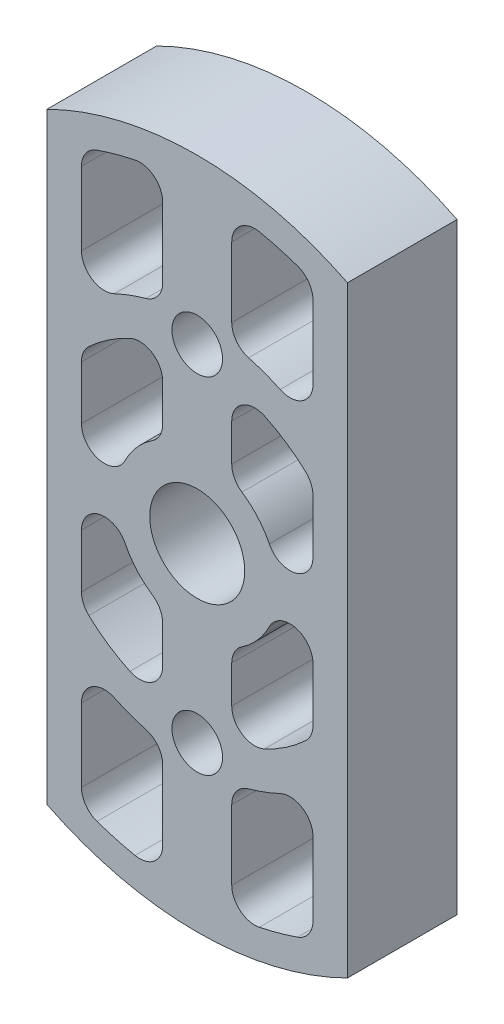
SolidWorks part; units mm, degrees
material "6061 Alloy"
ref_plane "Front Plane" through (0, 0, 0) normal (0, 0, 1) x (1, 0, 0)
ref_plane "Top Plane" through (0, 0, 0) normal (0, 1, 0) x (1, 0, 0)
ref_plane "Right Plane" through (0, 0, 0) normal (1, 0, 0) x (0, 0, -1)
sketch "Sketch1" plane through (0, 0, 0) normal (0, 0, 1) x (1, 0, 0)
  circle A0 centre (0, 0) radius 29.25
  dimension "D1" = 58.5
extrude "3/8" add sketch "Sketch1" along normal blind 9.525
sketch "Sketch2" plane through (0, 0, 9.525) normal (0, 0, 1) x (1, 0, 0)
  line L0 (0, 0) -> (0, 37.0794) construction
  line L1 (0, 0) -> (-34.7106, 0) construction
  line L2 (-3, 24.2193) -> (-3, 18.1547)
  line L3 (-10.0623, 23.3789) -> (-10.0623, 17.0174)
  line L4 (-3, 10.7221) -> (-3, 7.4833)
  line L5 (-10.0623, 8.6582) -> (-10.0623, 4)
  line L6 (3, 10.7221) -> (3, 7.4833)
  line L7 (10.0623, 8.6582) -> (10.0623, 4)
  line L8 (3, 24.2193) -> (3, 18.1547)
  line L9 (10.0623, 23.3789) -> (10.0623, 17.0174)
  line L10 (-3, -10.7221) -> (-3, -7.4833)
  line L11 (-10.0623, -8.6582) -> (-10.0623, -4)
  line L12 (3, -10.7221) -> (3, -7.4833)
  line L13 (10.0623, -8.6582) -> (10.0623, -4)
  line L14 (3, -24.2193) -> (3, -18.1547)
  line L15 (10.0623, -23.3789) -> (10.0623, -17.0174)
  line L16 (-3, -24.2193) -> (-3, -18.1547)
  line L17 (-10.0623, -23.3789) -> (-10.0623, -17.0174)
  arc A0 (-5.4044, 26.178) -> (-8.7143, 25.2696) centre (0, 0) ccw
  arc A1 (-4.469, 16.2265) -> (-7.206, 15.21) centre (0, 0) ccw
  circle A2 centre (0, 0) radius 29.25 construction
  arc A3 (-5.8453, 12.5347) -> (-9.4252, 10.1219) centre (0, 0) ccw
  arc A4 (-3.8889, 5.8204) -> (-6.2706, 3.1111) centre (0, 0) ccw
  arc A17 (-3, 7.4833) -> (-3.8889, 5.8204) centre (-5, 7.4833) cw
  arc A18 (-6.2706, 3.1111) -> (-10.0623, 4) centre (-8.0623, 4) cw
  arc A19 (-10.0623, 8.6582) -> (-9.4252, 10.1219) centre (-8.0623, 8.6582) cw
  arc A20 (-5.8453, 12.5347) -> (-3, 10.7221) centre (-5, 10.7221) cw
  arc A21 (-5.4044, 26.178) -> (-3, 24.2193) centre (-5, 24.2193) cw
  arc A22 (-8.7143, 25.2696) -> (-10.0623, 23.3789) centre (-8.0623, 23.3789) ccw
  arc A23 (-10.0623, 17.0174) -> (-7.206, 15.21) centre (-8.0623, 17.0174) ccw
  arc A24 (-4.469, 16.2265) -> (-3, 18.1547) centre (-5, 18.1547) ccw
  arc A25 (5.8453, 12.5347) -> (9.4252, 10.1219) centre (0, 0) cw
  arc A26 (5.8453, 12.5347) -> (3, 10.7221) centre (5, 10.7221) ccw
  arc A27 (3, 7.4833) -> (3.8889, 5.8204) centre (5, 7.4833) ccw
  arc A28 (3.8889, 5.8204) -> (6.2706, 3.1111) centre (0, 0) cw
  arc A29 (6.2706, 3.1111) -> (10.0623, 4) centre (8.0623, 4) ccw
  arc A30 (10.0623, 8.6582) -> (9.4252, 10.1219) centre (8.0623, 8.6582) ccw
  arc A31 (5.4044, 26.178) -> (8.7143, 25.2696) centre (0, 0) cw
  arc A32 (5.4044, 26.178) -> (3, 24.2193) centre (5, 24.2193) ccw
  arc A33 (4.469, 16.2265) -> (3, 18.1547) centre (5, 18.1547) cw
  arc A34 (4.469, 16.2265) -> (7.206, 15.21) centre (0, 0) cw
  arc A35 (8.7143, 25.2696) -> (10.0623, 23.3789) centre (8.0623, 23.3789) cw
  arc A36 (10.0623, 17.0174) -> (7.206, 15.21) centre (8.0623, 17.0174) cw
  arc A37 (-5.8453, -12.5347) -> (-9.4252, -10.1219) centre (0, 0) cw
  arc A38 (-5.8453, -12.5347) -> (-3, -10.7221) centre (-5, -10.7221) ccw
  arc A39 (-3, -7.4833) -> (-3.8889, -5.8204) centre (-5, -7.4833) ccw
  arc A40 (-3.8889, -5.8204) -> (-6.2706, -3.1111) centre (0, 0) cw
  arc A41 (-6.2706, -3.1111) -> (-10.0623, -4) centre (-8.0623, -4) ccw
  arc A42 (-10.0623, -8.6582) -> (-9.4252, -10.1219) centre (-8.0623, -8.6582) ccw
  arc A43 (5.8453, -12.5347) -> (3, -10.7221) centre (5, -10.7221) cw
  arc A44 (3, -7.4833) -> (3.8889, -5.8204) centre (5, -7.4833) cw
  arc A45 (3.8889, -5.8204) -> (6.2706, -3.1111) centre (0, 0) ccw
  arc A46 (6.2706, -3.1111) -> (10.0623, -4) centre (8.0623, -4) cw
  arc A47 (10.0623, -8.6582) -> (9.4252, -10.1219) centre (8.0623, -8.6582) cw
  arc A48 (5.8453, -12.5347) -> (9.4252, -10.1219) centre (0, 0) ccw
  arc A49 (5.4044, -26.178) -> (3, -24.2193) centre (5, -24.2193) cw
  arc A50 (4.469, -16.2265) -> (3, -18.1547) centre (5, -18.1547) ccw
  arc A51 (4.469, -16.2265) -> (7.206, -15.21) centre (0, 0) ccw
  arc A52 (10.0623, -17.0174) -> (7.206, -15.21) centre (8.0623, -17.0174) ccw
  arc A53 (8.7143, -25.2696) -> (10.0623, -23.3789) centre (8.0623, -23.3789) ccw
  arc A54 (5.4044, -26.178) -> (8.7143, -25.2696) centre (0, 0) ccw
  arc A55 (-5.4044, -26.178) -> (-8.7143, -25.2696) centre (0, 0) cw
  arc A56 (-5.4044, -26.178) -> (-3, -24.2193) centre (-5, -24.2193) ccw
  arc A57 (-4.469, -16.2265) -> (-3, -18.1547) centre (-5, -18.1547) cw
  arc A58 (-4.469, -16.2265) -> (-7.206, -15.21) centre (0, 0) cw
  arc A59 (-8.7143, -25.2696) -> (-10.0623, -23.3789) centre (-8.0623, -23.3789) cw
  arc A60 (-10.0623, -17.0174) -> (-7.206, -15.21) centre (-8.0623, -17.0174) cw
  point P24 (-3, 26.5611)
  point P31 (-3, 16.5611)
  point P41 (0, 0)
  point P107 (0, 0)
  dimension "D1" = 2.52
  dimension "D5" = 3
  dimension "D6" = 7
  dimension "D7" = 2
  dimension "D2" = 10
  dimension "D3" = 3
  dimension "D4" = 4
extrude "Cut-Extrude1" cut sketch "Sketch2" against normal up to surface (9.525 mm away) up to face at (29.25, 0, 0)
sketch "Sketch3" plane through (0, 0, 9.525) normal (0, 0, 1) x (1, 0, 0)
  line L0 (0, 15) -> (0, 0) construction
  circle A0 centre (0, 15) radius 2.2
  circle A1 centre (0, -15) radius 2.2
  point P12 (0, 0)
  dimension "D1" = 4.4
  dimension "D2" = 15
  dimension "D3" = 2
extrude "M4_through" cut sketch "Sketch3" against normal up to surface (9.525 mm away) up to face at (-6.4532, -7.7476, 0)
sketch "Sketch4" plane through (0, 0, 9.525) normal (0, 0, 1) x (1, 0, 0)
  circle A0 centre (0, 0) radius 4.1275
  dimension "D1" = 8.255
extrude "3/8_-16-DRILL" cut sketch "Sketch4" against normal up to surface (9.525 mm away) up to face at (2.2, 15, 0)
sketch "Sketch6" plane through (0, 0, 9.525) normal (0, 0, 1) x (1, 0, 0)
  line L0 (-10.0623, 23.3789) -> (-10.0623, 17.0174) construction
  line L1 (-31.0916, 27.4538) -> (-13.0623, 27.4538)
  line L2 (-31.0916, 27.4538) -> (-31.0916, -30.1261)
  line L3 (-31.0916, -30.1261) -> (-13.0623, -30.1261)
  line L4 (-13.0623, 27.4538) -> (-13.0623, -30.1261)
  line L5 (-22.0769, -30.1261) -> (-22.0769, 27.4538) construction
  line L6 (-31.0916, -1.3362) -> (-13.0623, -1.3362) construction
  line L7 (0, 0) -> (0, 9.1394) construction
  line L8 (31.0916, -30.1261) -> (13.0623, -30.1261)
  line L9 (13.0623, 27.4538) -> (13.0623, -30.1261)
  line L10 (31.0916, 27.4538) -> (13.0623, 27.4538)
  line L11 (31.0916, 27.4538) -> (31.0916, -30.1261)
  point P432 (-22.0769, -1.3362)
  dimension "D1" = 3
extrude "Cut-Extrude2" cut sketch "Sketch6" against normal up to surface (9.525 mm away) up to face at (4.1275, 0, 0)
